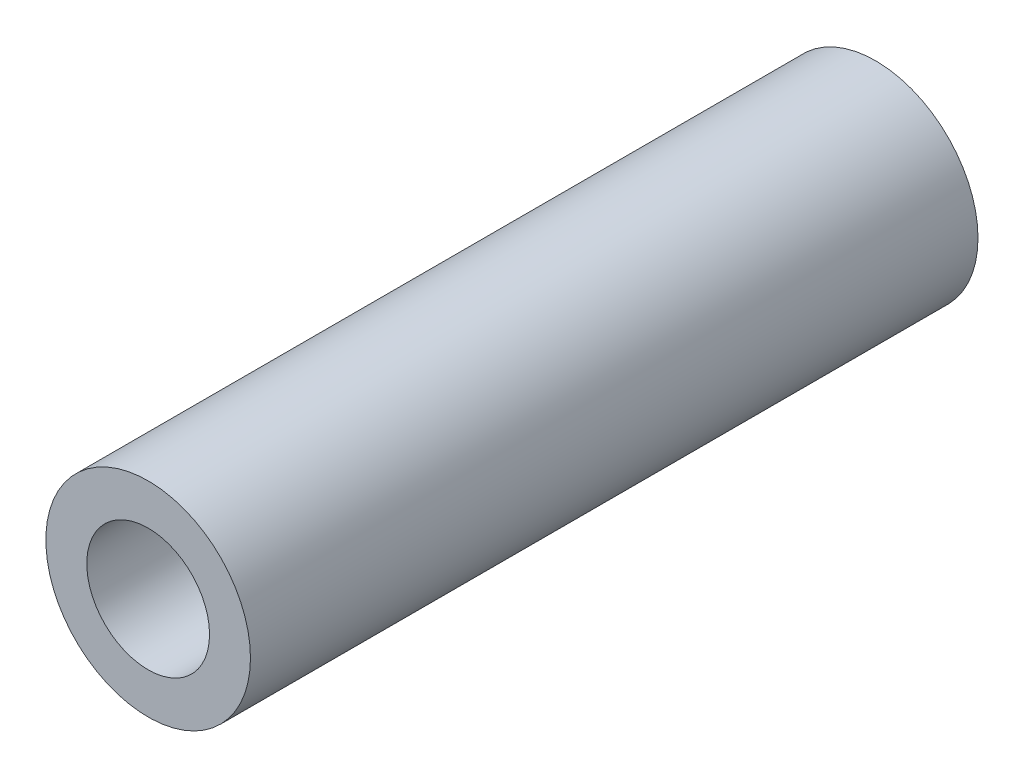
SolidWorks part; units mm, degrees
ref_plane "Front Plane" through (0, 0, 0) normal (0, 0, 1) x (1, 0, 0)
ref_plane "Top Plane" through (0, 0, 0) normal (0, 1, 0) x (1, 0, 0)
ref_plane "Right Plane" through (0, 0, 0) normal (1, 0, 0) x (0, 0, -1)
sketch "Cross Section Sketch" plane through (0, 0, 0) normal (0, 0, 1) x (1, 0, 0)
  circle A0 centre (0, 0) radius 2.25
  circle A1 centre (0, 0) radius 1.35
  dimension "OD" = 4.5
  dimension "ID" = 2.7
extrude "Extrude Length" add sketch "Cross Section Sketch" along normal mid plane 16
